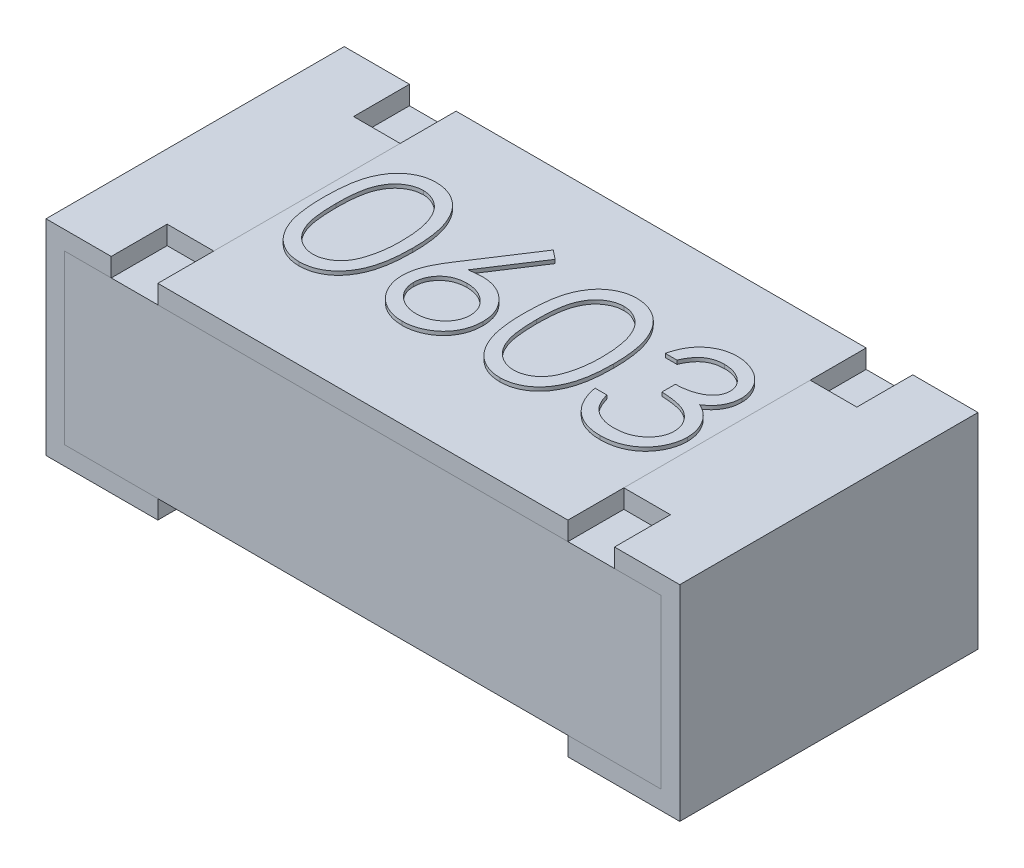
SolidWorks part; units mm, degrees
ref_plane "Front Plane" through (0, 0, 0) normal (0, 0, 1) x (1, 0, 0)
ref_plane "Top Plane" through (0, 0, 0) normal (0, 1, 0) x (1, 0, 0)
ref_plane "Right Plane" through (0, 0, 0) normal (1, 0, 0) x (0, 0, -1)
sketch "Croquis1" plane through (0, 0, 0) normal (0, 1, 0) x (1, 0, 0)
  line L1 (0.8, 0.4) -> (-0.8, 0.4)
  line L2 (0.8, 0.4) -> (0.8, -0.4)
  line L3 (0.8, -0.4) -> (-0.8, -0.4)
  line L4 (-0.8, 0.4) -> (-0.8, -0.4)
  line L5 (0.8, 0.4) -> (-0.8, -0.4) construction
  line L6 (0.8, -0.4) -> (-0.8, 0.4) construction
  point P0 (0, 0)
  dimension "D1" = 0.8
  dimension "D2" = 1.6
extrude "Extruir1" add sketch "Croquis1" along normal blind 0.5
sketch "Croquis2" plane through (0, 0, 0.4) normal (0, 0, 1) x (1, 0, 0)
  line L0 (0.8, 0.5) -> (0.8, 0) construction
  line L1 (-0.8, 0) -> (0.8, 0)
  line L2 (-0.8, 0) -> (-0.8, 0.05)
  line L3 (-0.8, 0.05) -> (0.8, 0.05)
  line L4 (0.8, 0) -> (0.8, 0.05)
  dimension "D1" = 0.05
extrude "Extruir2" cut sketch "Croquis2" against normal through all
sketch "Croquis3" plane through (0, 0, 0.4) normal (0, 0, 1) x (1, 0, 0)
  line L0 (-0.55, 0.55) -> (-0.85, 0.55)
  line L1 (-0.85, 0.55) -> (-0.85, 0)
  line L2 (-0.85, 0) -> (-0.55, 0)
  line L4 (-0.8, 0.5) -> (-0.8, 0.05) construction
  line L5 (-0.8, 0.5) -> (0.8, 0.5) construction
  dimension "D1" = 0.05
  dimension "D2" = 0.05
  dimension "D3" = 0.3
  dimension "D4" = 0.3
  dimension "D5" = 0.55
sketch3d "Croquis3D1"
  line L0 (-0.55, 0.55, 0.4) -> (-0.55, 0.55, -0.4)
  line L1 (-0.55, 0.55, -0.4) -> (-0.55, 0.5, -0.4)
  line L2 (-0.55, 0.5, -0.4) -> (-0.55, 0.5, 0.4)
  line L3 (-0.55, 0.5, 0.4) -> (-0.55, 0.55, 0.4)
  line L4 (-0.8, 0.5, -0.4) -> (-0.8, 0.5, 0.4) construction
  dimension "D1" = 0.3
sweep "Barrer1" add profiles "Croquis3D1" path "Croquis3"
ref_plane "Plano1" through (0, 0.5, 0.4) normal (1, 0, 0) x (0, 0, -1)
mirror "Simetría1" about plane through (0, 0.5, 0.4) normal (1, 0, 0) of bodies 104
sketch "Croquis4" plane through (-0.55, 0, 0) normal (1, 0, 0) x (0, 0, -1)
  line L1 (-0.4, 0.55) -> (0.4, 0.55)
  line L2 (-0.4, 0.55) -> (-0.4, 0.5)
  line L3 (-0.4, 0.5) -> (0.4, 0.5)
  line L4 (0.4, 0.55) -> (0.4, 0.5)
extrude "Extruir3" add sketch "Croquis4" along normal up to surface (1.1 mm away) separate body up to face at (0.55, 0.525, 0)
sketch "Croquis5" plane through (0, 0.55, 0) normal (0, 1, 0) x (1, 0, 0)
  line L0 (0, -0.4) -> (0, 0.4) construction
  line L1 (-0.55, -0.4) -> (-0.675, -0.4)
  line L2 (-0.55, -0.4) -> (-0.55, -0.25)
  line L3 (-0.55, -0.25) -> (-0.675, -0.25)
  line L4 (-0.675, -0.4) -> (-0.675, -0.25)
  line L5 (0.55, -0.4) -> (-0.55, -0.4) construction
  line L6 (0.55, 0.4) -> (-0.55, 0.4) construction
  line L7 (-0.55, 0) -> (0.55, 0) construction
  line L8 (-0.55, 0.4) -> (-0.55, -0.4) construction
  line L9 (0.55, 0.4) -> (0.55, -0.4) construction
  line L10 (-0.675, 0.4) -> (-0.675, 0.25)
  line L11 (-0.55, 0.25) -> (-0.675, 0.25)
  line L12 (-0.55, 0.4) -> (-0.55, 0.25)
  line L13 (-0.55, 0.4) -> (-0.675, 0.4)
  line L14 (0.55, 0.4) -> (0.675, 0.4)
  line L15 (0.55, 0.4) -> (0.55, 0.25)
  line L16 (0.55, 0.25) -> (0.675, 0.25)
  line L17 (0.675, 0.4) -> (0.675, 0.25)
  line L18 (0.675, -0.4) -> (0.675, -0.25)
  line L19 (0.55, -0.25) -> (0.675, -0.25)
  line L20 (0.55, -0.4) -> (0.55, -0.25)
  line L21 (0.55, -0.4) -> (0.675, -0.4)
  dimension "D1" = 0.15
  dimension "D2" = 0.125
extrude "Extruir4" cut sketch "Croquis5" against normal up to next (0.05 mm away)
sketch "Sketch1" plane through (0, 0.55, 0) normal (0, 1, 0) x (1, 0, 0)
  text T0 "0603" font "Century Gothic" height 0.35
extrude "Boss-Extrude1" add sketch "Sketch1" along normal blind 0.01
